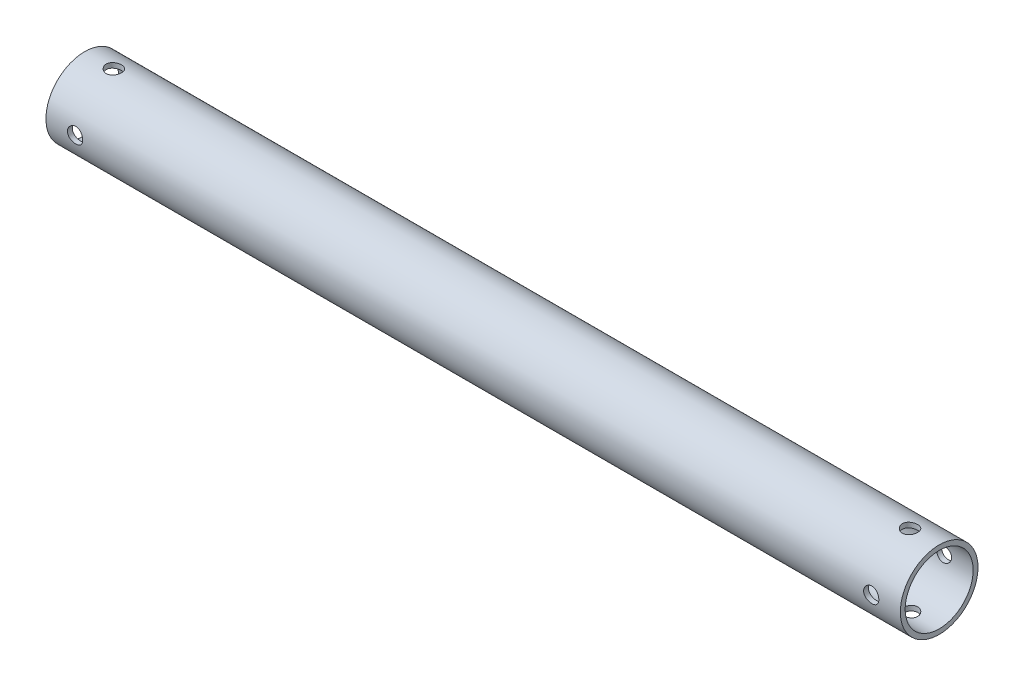
SolidWorks part; units mm, degrees
material "PC High Viscosity"
ref_plane "Front Plane" through (0, 0, 0) normal (0, 0, 1) x (1, 0, 0)
ref_plane "Top Plane" through (0, 0, 0) normal (0, 1, 0) x (1, 0, 0)
ref_plane "Right Plane" through (0, 0, 0) normal (1, 0, 0) x (0, 0, -1)
sketch "Sketch1" plane through (0, 0, 0) normal (1, 0, 0) x (0, 0, -1)
  circle A0 centre (0, 0) radius 12.7
  dimension "D1" = 25.4
extrude "Extrude-Thin1" add sketch "Sketch1" along normal mid plane 279.4 thin thin type one direction reverse wall 1.5875
sketch "Sketch2" plane through (0, 0, 0) normal (0, 0, 1) x (1, 0, 0)
  line L0 (-139.7, -12.7) -> (139.7, -12.7) construction
  line L1 (77.425, -12.7) -> (98.425, -12.7)
  line L2 (77.425, -12.7) -> (77.425, 12.7)
  line L3 (77.425, 12.7) -> (98.425, 12.7)
  line L4 (98.425, -12.7) -> (98.425, 12.7)
  line L5 (139.7, 12.7) -> (-139.7, 12.7) construction
  line L6 (139.7, -12.7) -> (139.7, 12.7) construction
  line L7 (0, 0) -> (0, 11.1276) construction
  line L8 (-98.425, -12.7) -> (-98.425, 12.7)
  line L9 (-77.425, 12.7) -> (-98.425, 12.7)
  line L10 (-77.425, -12.7) -> (-77.425, 12.7)
  line L11 (-77.425, -12.7) -> (-98.425, -12.7)
  line L13 (139.7, -12.7) -> (137.3759, -12.7)
  line L14 (139.7, -12.7) -> (139.7, 12.7)
  line L15 (139.7, 12.7) -> (137.3759, 12.7)
  line L16 (137.3759, -12.7) -> (137.3759, 12.7)
  dimension "D1" = 41.275
  dimension "D2" = 21
  dimension "D3" = 2.3241
sketch "Sketch3" plane through (0, 0, 0) normal (0, 0, 1) x (1, 0, 0)
  line L0 (139.7, -11.1125) -> (139.7, 11.1125) construction
  line L1 (-139.7, 12.7) -> (-139.7, -12.7) construction
  circle A0 centre (130.175, 0) radius 2.4892
  circle A1 centre (-130.175, 0) radius 2.4892
  dimension "D1" = 4.9784
  dimension "D2" = 9.525
  dimension "D3" = 9.525
extrude "Cut-Extrude1" cut sketch "Sketch3" against normal through all both and the other way through all
sketch "Sketch4" plane through (0, 0, 0) normal (0, 1, 0) x (1, 0, 0)
  line L0 (139.7, -11.1125) -> (139.7, 11.1125) construction
  line L1 (0, 12.7) -> (0, -12.7) construction
  line L2 (-127.6858, -12.7) -> (127.6858, -12.7) construction
  line L3 (127.6858, 12.7) -> (-127.6858, 12.7) construction
  circle A0 centre (130.175, 0) radius 2.4892
  circle A1 centre (-130.175, 0) radius 2.4892
  dimension "D1" = 4.9784
  dimension "D2" = 9.525
extrude "Cut-Extrude2" cut sketch "Sketch4" against normal through all both and the other way through all
equation "\"D2@Sketch2\"=21mm"
